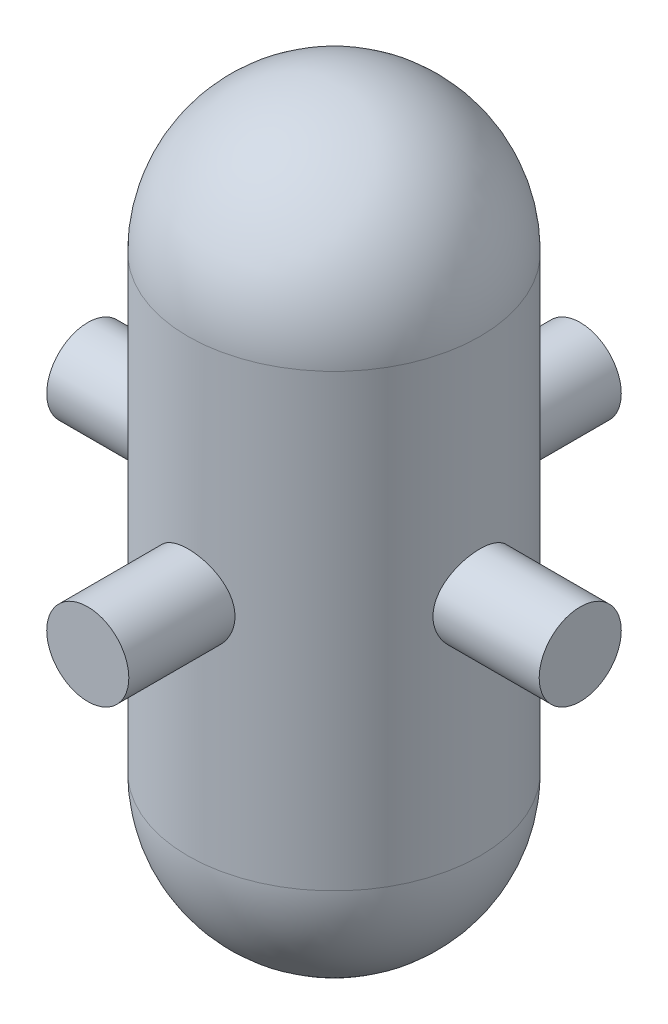
SolidWorks part; units mm, degrees
note: The reader was unsure of these and kept them because the rebuilt part matched: shared geometry of "Sketch1<3>".
ref_plane "Front" through (0, 0, 0) normal (0, 0, 1) x (1, 0, 0)
ref_plane "Top" through (0, 0, 0) normal (0, 1, 0) x (1, 0, 0)
ref_plane "Right" through (0, 0, 0) normal (1, 0, 0) x (0, 0, -1)
sketch "Sketch1" plane through (0, 0, 0) normal (0, 0, 1) x (1, 0, 0)
  line L1 (80, 123.33) -> (80, 0)
  line L4 (0, 0) -> (80, 0) construction
  line L5 (70, 113.33) -> (70, 0)
  line L6 (0, 203.33) -> (0, 193.33)
  line L7 (80, 0) -> (70, 0)
  line L8 (0, -203.33) -> (0, -193.33)
  line L9 (70, -123.33) -> (70, 0)
  line L10 (80, -123.33) -> (80, 0)
  line L11 (70, 123.33) -> (80, 123.33)
  line L12 (70, 123.33) -> (70, 0) construction
  line L13 (0, 123.33) -> (80, 123.33)
  line L14 (0, 123.33) -> (0, 113.33)
  line L15 (0, 113.33) -> (80, 113.33)
  line L16 (80, 123.33) -> (80, 113.33)
  arc A0 (0, 203.33) -> (80, 123.33) centre (0, 123.33) cw
  arc A4 (0, 193.33) -> (70, 123.33) centre (0, 123.33) cw
  arc A5 (0, -193.33) -> (70, -123.33) centre (0, -123.33) ccw
  arc A6 (0, -203.33) -> (80, -123.33) centre (0, -123.33) ccw
  dimension "D1" = 80
  dimension "D2" = 123.33
  dimension "D4" = 10
  dimension "D3" = 10
revolve "Revolve1" add sketch "Sketch1" angle 360 about L6
revolve "Revolve2" add sketch "Sketch1<3>" angle 360 about L6
sketch "Sketch1<3>" plane through (0, 0, 0) normal (0, 0, 1) x (1, 0, 0) same geometry as "Sketch1"
sketch "Sketch3" plane through (0, 0, 0) normal (0, 0, 1) x (1, 0, 0)
  circle A0 centre (0, 0) radius 22.5
  dimension "D1" = 45
extrude "Boss-Extrude1" add sketch "Sketch3" along normal mid plane 270 separate body
sketch "Sketch5" plane through (0, 0, 0) normal (1, 0, 0) x (0, 0, -1)
  circle A0 centre (0, 0) radius 22.5
  dimension "D1" = 45
extrude "Boss-Extrude3" add sketch "Sketch5" along normal mid plane 270
sketch "Sketch6" plane through (0, 0, 0) normal (0, 1, 0) x (1, 0, 0)
  circle A0 centre (0, 0) radius 70
  dimension "D1" = 140
extrude "Cut-Extrude1" cut sketch "Sketch6" against normal mid plane 50
